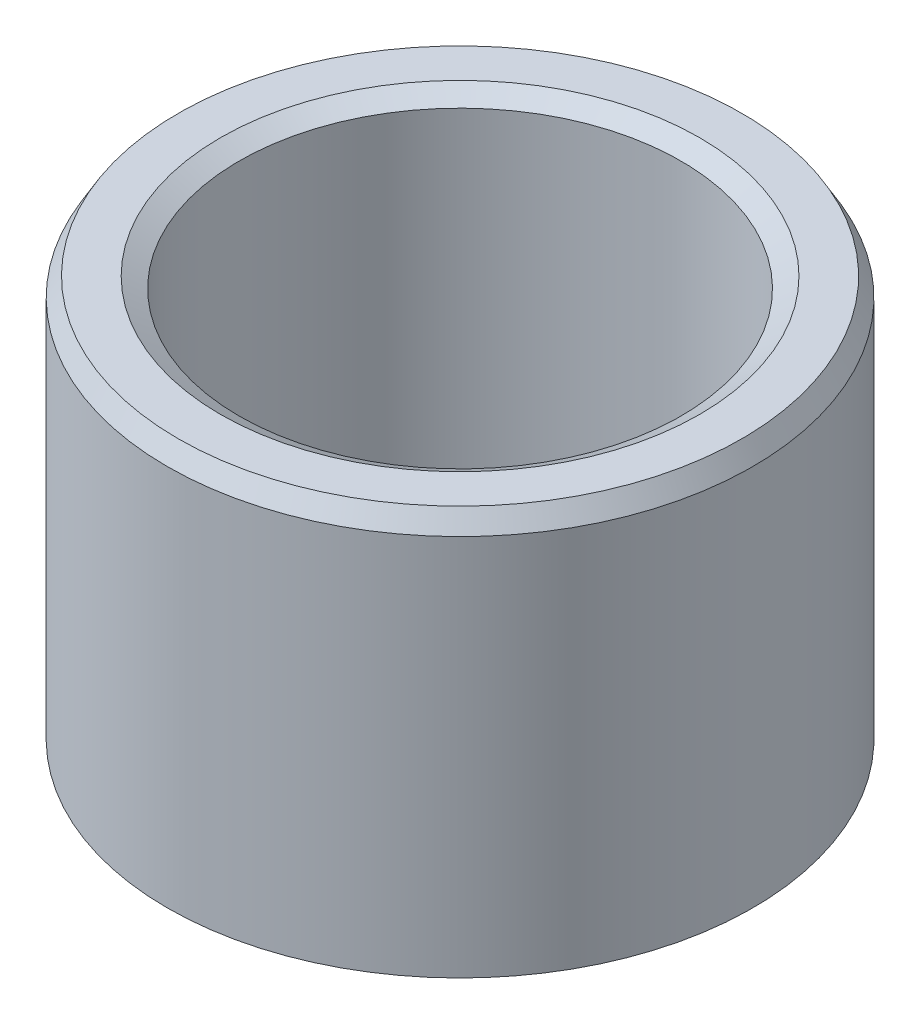
SolidWorks part; units mm, degrees
ref_plane "Front Plane" through (0, 0, 0) normal (0, 0, 1) x (1, 0, 0)
ref_plane "Top Plane" through (0, 0, 0) normal (0, 1, 0) x (1, 0, 0)
ref_plane "Right Plane" through (0, 0, 0) normal (1, 0, 0) x (0, 0, -1)
sketch "Sketch1" plane through (0, 0, 0) normal (0, 1, 0) x (1, 0, 0)
  circle A0 centre (0, 0) radius 50
  dimension "SLEEVE_OD" = 100
extrude "Boss-Extrude1" add sketch "Sketch1" along normal blind 70.3519
sketch "Sketch2" plane through (0, 0, 0) normal (0, 1, 0) x (1, 0, 0)
  circle A0 centre (0, 0) radius 37.7449
  dimension "BORE_D" = 75.4897
extrude "Cut-Extrude1" cut sketch "Sketch2" along normal through all
chamfer "Chamfer1" distance 3.1993 angle 30 4 edges at (0, 70.3519, 37.7449) (0, 0, 37.7449) (0, 0, 50) (0, 70.3519, 50) first distance on face at (0, 70.3519, 37.7449) first distance on face at (0, 0, 37.7449) first distance on face at (0, 70.3519, 50)
